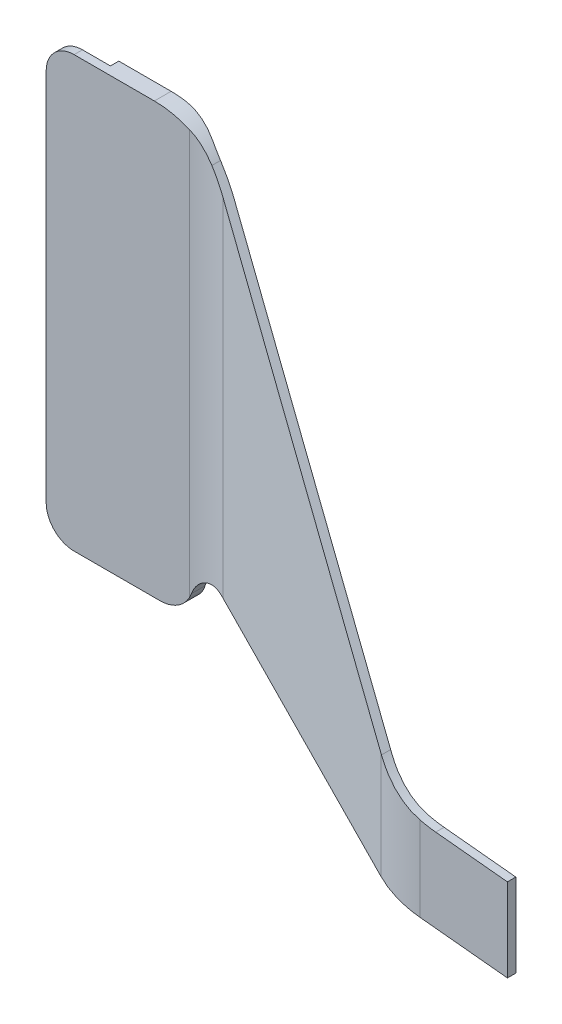
SolidWorks part; units mm, degrees
ref_plane "前视基准面" through (0, 0, 0) normal (0, 0, 1) x (1, 0, 0)
ref_plane "上视基准面" through (0, 0, 0) normal (0, 1, 0) x (1, 0, 0)
ref_plane "右视基准面" through (0, 0, 0) normal (1, 0, 0) x (0, 0, -1)
other "Configuration Table"
sketch "草图3" plane through (0, 0, 0) normal (0, 1, 0) x (1, 0, 0)
  line L0 (-47.4227, 12.2165) -> (-21.7733, 12.2165)
  line L1 (-13.4652, 10.4093) -> (38.6199, -13.3763)
  line L2 (46.9279, -15.1835) -> (62.5773, -15.1835)
  arc A0 (38.6199, -13.3763) -> (46.9279, -15.1835) centre (46.9279, 4.8165) ccw
  arc A1 (-21.7733, 12.2165) -> (-13.4652, 10.4093) centre (-21.7733, -7.7835) cw
  point P6 (42.5773, -15.1835)
  point P9 (-17.4227, 12.2165)
  dimension "D5" = 20
  dimension "D1" = 30
  dimension "D2" = 20
  dimension "D3" = 60
  dimension "D4" = 27.4
extrude "拉伸-薄壁1" add sketch "草图3" along normal blind 77 thin thin type one direction wall 1.5
sketch "草图4" plane through (0, 0, 0) normal (0, 0, 1) x (1, 0, 0)
  line L0 (-21.7733, 77) -> (38.133, 21.4368)
  line L1 (49.7322, 16.2008) -> (62.5773, 14.909)
  line L2 (62.5773, 77) -> (62.5773, 0) construction
  line L3 (62.5773, 14.909) -> (62.5773, 77)
  line L4 (62.5773, 77) -> (-21.7733, 77)
  line L5 (-21.7733, 8.4832) -> (62.5773, 0)
  line L6 (-21.7733, 77) -> (-21.7733, 0) construction
  line L7 (-21.7733, 8.4832) -> (-21.7733, 0)
  line L8 (-21.7733, 0) -> (62.5773, 0)
  arc A0 (38.133, 21.4368) -> (49.7322, 16.2008) centre (51.7336, 36.1004) ccw
  dimension "D1" = 20
extrude "切除-拉伸1" cut sketch "草图4" against normal mid plane 50
fillet "圆角1" radius 6 1 edges at (-21.7733, 8.4832, -11.4665)
fillet "圆角2" radius 6 1 edges at (-21.7733, 0, -11.4665)
fillet "圆角3" radius 16 1 edges at (-21.7733, 77, -11.4665)
sketch "草图5" plane through (0, 0, -12.2165) normal (0, 0, -1) x (-1, 0, 0)
  line L8 (47.4227, 77) -> (28.051, 77)
  line L9 (21.7733, 75.717) -> (21.7733, 3.1123)
  line L10 (27.0326, 0) -> (47.4227, 0)
  line L11 (47.4227, 0) -> (47.4227, 77)
  line L12 (37.4227, 77) -> (28.051, 77)
  line L13 (21.7733, 75.717) -> (21.7733, 3.1123)
  line L14 (27.0326, 0) -> (37.4227, 0)
  line L16 (37.4227, 77) -> (37.4227, 0)
  arc A4 (28.051, 77) -> (21.7733, 75.717) centre (28.051, 61) ccw
  arc A5 (21.7733, 3.1123) -> (27.0326, 0) centre (27.0326, 6) ccw
  arc A6 (28.051, 77) -> (21.7733, 75.717) centre (28.051, 61) ccw
  arc A7 (21.7733, 3.1123) -> (27.0326, 0) centre (27.0326, 6) ccw
  dimension "D2" = 10
  dimension "D1" = 0
extrude "凸台-拉伸1" add sketch "草图5" along normal blind 1.5
fillet "圆角4" radius 16 1 edges at (-21.7733, 39.4146, -12.2165)
fillet "圆角5" radius 16 1 edges at (-21.7733, 39.4146, -13.7165)
fillet "圆角6" radius 5 2 edges at (-47.4227, 0, -11.4665) (-47.4227, 77, -11.4665)
